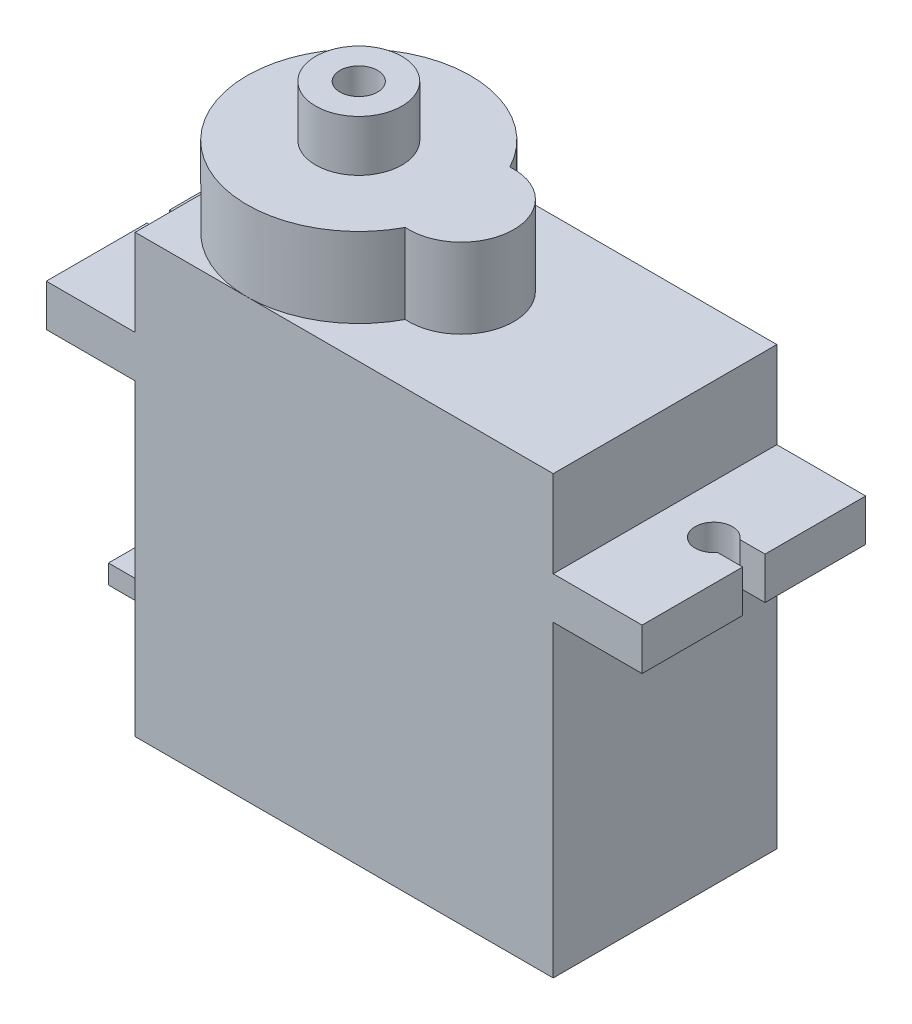
SolidWorks part; units mm, degrees
ref_plane "Front Plane" through (0, 0, 0) normal (0, 0, 1) x (1, 0, 0)
ref_plane "Top Plane" through (0, 0, 0) normal (0, 1, 0) x (1, 0, 0)
ref_plane "Right Plane" through (0, 0, 0) normal (1, 0, 0) x (0, 0, -1)
sketch "Sketch1" plane through (0, 0, 0) normal (0, 1, 0) x (1, 0, 0)
  line L1 (0, 0) -> (22.7711, 0)
  line L2 (0, 0) -> (0, 12.18)
  line L3 (0, 12.18) -> (22.7711, 12.18)
  line L4 (22.7711, 0) -> (22.7711, 12.18)
  dimension "D1" = 12.18
  dimension "D2" = 22.7711
extrude "Boss-Extrude1" add sketch "Sketch1" along normal blind 23.79
ref_plane "Plane1" through (0, 19.0656, 0) normal (0, 1, 0) x (1, 0, 0)
sketch "Sketch3" plane through (0, 19.0656, 0) normal (0, 1, 0) x (1, 0, 0)
  line L0 (22.7711, 12.18) -> (0, 12.18) construction
  line L1 (-4.8387, 0) -> (27.6098, 0)
  line L2 (-4.8387, 0) -> (-4.8387, 12.18)
  line L3 (-4.8387, 12.18) -> (27.6098, 12.18)
  line L4 (27.6098, 0) -> (27.6098, 12.18)
  line L5 (0, 0) -> (22.7711, 0) construction
  point P6 (11.3856, 0)
  point P9 (11.3856, 0)
  dimension "D1" = 32.4485
extrude "Boss-Extrude2" add sketch "Sketch3" against normal blind 2.286
sketch "Sketch4" plane through (0, 19.0656, 0) normal (0, 1, 0) x (1, 0, 0)
  line L0 (-3.4671, 6.6996) -> (-3.4671, 5.4804) construction
  line L1 (-4.8387, 6.6996) -> (-3.4671, 6.6996)
  line L2 (-4.8387, 12.18) -> (-4.8387, 0) construction
  line L3 (-3.4671, 5.4804) -> (-4.8387, 5.4804)
  line L4 (-1.6383, 6.09) -> (-1.6383, 8.3545) construction
  line L5 (11.3856, 12.18) -> (11.3856, 0) construction
  line L6 (22.7711, 12.18) -> (0, 12.18) construction
  line L7 (0, 0) -> (22.7711, 0) construction
  line L8 (24.4094, 6.09) -> (24.4094, 8.3545) construction
  line L9 (26.2382, 6.6996) -> (26.2382, 5.4804) construction
  line L10 (26.2382, 5.4804) -> (27.6098, 5.4804)
  line L11 (27.6098, 6.6996) -> (26.2382, 6.6996)
  line L12 (-4.8387, 6.6996) -> (-4.8387, 5.4804)
  line L13 (27.6098, 6.6996) -> (27.6098, 5.4804)
  arc A0 (-3.4671, 6.6996) -> (-3.4671, 5.4804) centre (-2.6543, 6.09) cw
  arc A1 (26.2382, 6.6996) -> (26.2382, 5.4804) centre (25.4254, 6.09) ccw
  point P6 (-3.4671, 6.09)
  point P8 (-4.8387, 6.09)
  dimension "D1" = 1.016
  dimension "D2" = 3.2004
  dimension "D3" = 1.2192
extrude "Cut-Extrude1" cut sketch "Sketch4" against normal through all
sketch "Sketch5" plane through (0, 23.79, 0) normal (0, 1, 0) x (1, 0, 0)
  line L0 (22.7711, 12.18) -> (0, 12.18) construction
  line L1 (0, 12.18) -> (0, 0) construction
  line L2 (0, 0) -> (22.7711, 0) construction
  line L3 (14.5288, 6.09) -> (14.5288, 9.2952) construction
  arc A0 (11.4717, 8.9405) -> (11.4717, 3.2395) centre (6.09, 6.09) ccw
  arc A1 (11.4717, 3.2395) -> (11.4717, 8.9405) centre (11.6713, 6.09) ccw
  dimension "D1" = 14.5288
  dimension "D2" = 5.715
extrude "Boss-Extrude3" add sketch "Sketch5" along normal blind 4.3434
sketch "Sketch6" plane through (0, 28.1334, 0) normal (0, 1, 0) x (1, 0, 0)
  circle A0 centre (6.09, 6.09) radius 2.3495
  arc A1 (11.4717, 8.9405) -> (11.4717, 3.2395) centre (6.09, 6.09) ccw construction
  dimension "D1" = 4.699
extrude "Boss-Extrude4" add sketch "Sketch6" along normal blind 2.7813 contours A0
sketch "Sketch7" plane through (0, 0, 0) normal (-1, 0, 0) x (0, 0, 1)
  line L0 (-12.18, 0) -> (0, 0) construction
  line L1 (-7.5378, 1.78) -> (-4.6422, 1.78)
  line L2 (-7.5378, 1.78) -> (-7.5378, 2.8214)
  line L3 (-7.5378, 2.8214) -> (-4.6422, 2.8214)
  line L4 (-4.6422, 1.78) -> (-4.6422, 2.8214)
  point P4 (-6.09, 1.78)
  point P7 (-6.09, 0)
  dimension "D1" = 1.0414
  dimension "D2" = 2.8956
  dimension "D3" = 1.78
extrude "Boss-Extrude5" add sketch "Sketch7" along normal blind 6.096
ref_axis "Axis1" through (6.09, 30.9147, -6.09) along (0, -1, 0)
ref_plane "Plane2" through (6.09, 0, 0) normal (-1, 0, 0) x (0, 0, 1)
sketch "Sketch8" plane through (0, 28.1334, 0) normal (0, 1, 0) x (1, 0, 0)
  circle A0 centre (6.09, 6.09) radius 3.556
  dimension "D1" = 7.112
extrude "Boss-Extrude6" [suppressed] add sketch "Sketch8" along normal blind 4.4577
sketch "Sketch9" [suppressed] plane through (0, 31.9532, 0) normal (0, 1, 0) x (1, 0, 0)
  line L0 (2.5019, 6.0579) -> (3.8735, 18.5674)
  line L1 (3.8735, 18.5674) -> (8.2423, 18.5674)
  line L2 (8.2423, 18.5674) -> (9.6139, 6.0579)
  line L3 (6.0579, 6.0579) -> (6.0579, 18.5674) construction
  line L4 (2.5019, 6.0579) -> (9.6139, 6.0579)
  line L5 (8.9281, 12.3127) -> (6.0579, 12.3127) construction
  line L6 (6.0579, 12.3127) -> (3.1877, 12.3127) construction
  circle A0 centre (6.0579, 6.0579) radius 3.556 construction
  point P10 (6.0579, 18.5674)
  point P18 (6.0579, 2.5019)
  dimension "D1" = 4.3688
  dimension "D2" = 16.0655
extrude "Boss-Extrude7" [suppressed] add sketch "Sketch9" against normal blind 1.651
sketch "Sketch11" [suppressed] plane through (0, 31.9532, 0) normal (0, 1, 0) x (1, 0, 0)
  circle A0 centre (6.0579, 6.0579) radius 2.4257
  arc A1 (2.5864, 6.8284) -> (9.5294, 6.8284) centre (6.0579, 6.0579) ccw construction
  dimension "D1" = 4.8514
extrude "Cut-Extrude2" [suppressed] cut sketch "Sketch11" against normal blind 2.54
sketch "Sketch12" [suppressed] plane through (0, 29.4132, 0) normal (0, 1, 0) x (1, 0, 0)
  circle A0 centre (6.0579, 6.0579) radius 1.2001
  dimension "D1" = 2.4003
extrude "Cut-Extrude3" [suppressed] cut sketch "Sketch12" against normal up to surface (1.9177 mm away) up to face at (6.09, 28.1334, -3.7405)
hole_wizard "M2.5x0.45 Tapped Hole1" positions "Sketch14" profile "Sketch15" tap size "M2.5x0.45" standard "ANSI Metric"
sketch "Sketch14" plane through (0, 30.9147, 0) normal (0, 1, 0) x (1, 0, 0)
  point P0 (6.09, 6.09)
sketch "Sketch15" plane through (6.09, 30.9147, -6.09) normal (1, 0, 0) x (0, 0, 1)
  line L0 (0, 0) -> (0, 4.6159)
  line L1 (0, 4.6159) -> (1.025, 4)
  line L2 (1.025, 4) -> (1.025, 0)
  line L5 (1.025, 0) -> (0, 0)
  line L10 (0, 4.6159) -> (-1.025, 4) construction
  line L11 (0, -6.35) -> (0, 107.95) construction
  dimension "Tap Drill Dia." = 2.05
  dimension "Tap Drill Depth" = 4
  dimension "Drill Angle" = 118
cosmetic thread "Hole Thread1" parameters "D1"=4, "D2"=2.5
ref_plane "Plane3" through (0, 26.2988, 0) normal (0, 1, 0) x (1, 0, 0)
